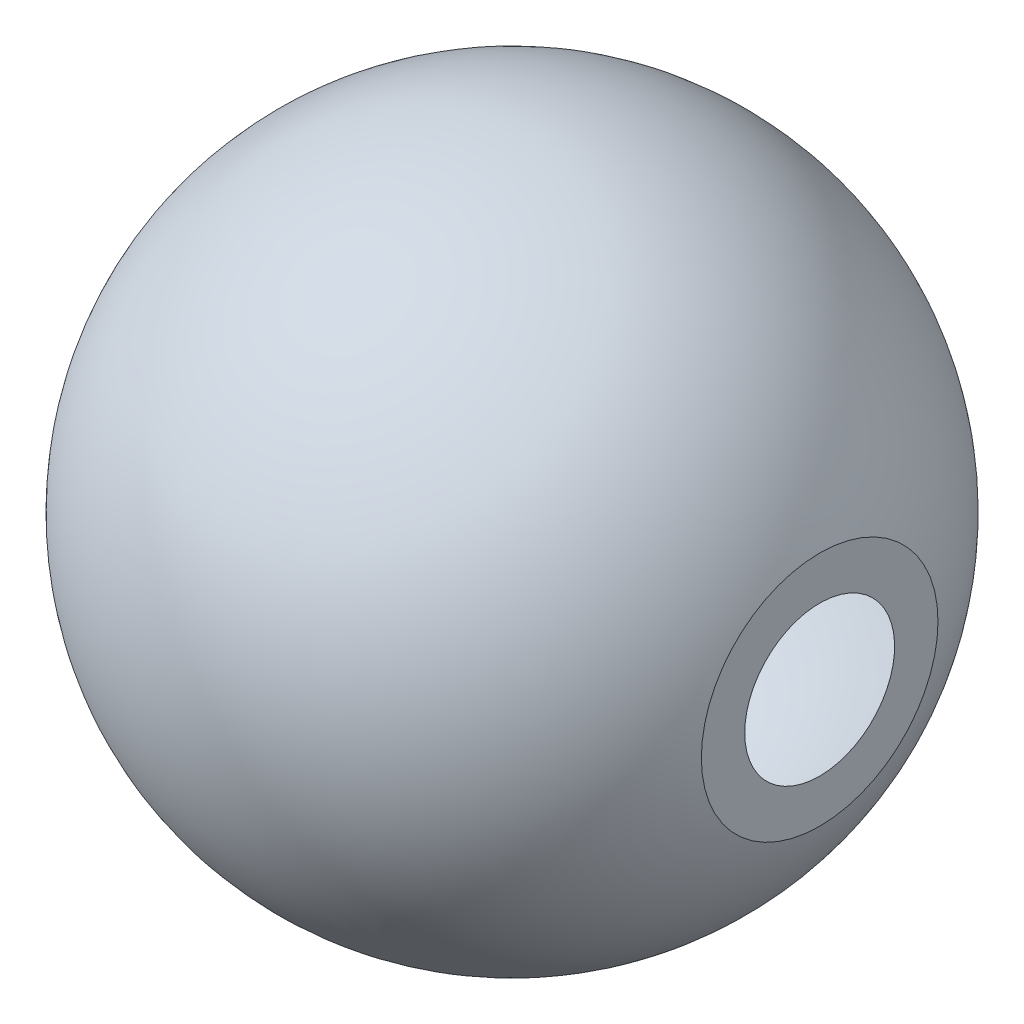
SolidWorks part; units mm, degrees
ref_plane "Front Plane" through (0, 0, 0) normal (0, 0, 1) x (1, 0, 0)
ref_plane "Top Plane" through (0, 0, 0) normal (0, 1, 0) x (1, 0, 0)
ref_plane "Right Plane" through (0, 0, 0) normal (1, 0, 0) x (0, 0, -1)
sketch "Sketch2" plane through (0, 0, 0) normal (0, 0, 1) x (1, 0, 0)
  line L1 (-76.2, 0) -> (-73.2, 0)
  line L3 (71.12, 17.3259) -> (71.12, 27.3567)
  arc A2 (71.12, 17.3259) -> (-73.2, 0) centre (0, 0) ccw
  spline S0 degree 4 poles (-76.2, 0) (-76.1997, 3.3499) (-75.8605, 9.1425) (-74.5492, 17.2684) (-71.3778, 27.3961) (-67.3503, 36.1749) (-62.292, 44.3214) (-56.2535, 51.7709) (-49.3299, 58.4059) (-41.6302, 64.1219) (-33.2754, 68.829) (-24.3971, 72.4532) (-15.1349, 74.9374) (-5.6389, 76.242) (3.9415, 76.3482) (13.4556, 75.2562) (22.7546, 72.9848) (31.6968, 69.5691) (40.1421, 65.0628) (47.958, 59.5363) (55.022, 53.0767) (61.2234, 45.7846) (66.4649, 37.7755) (70.6909, 29.1183) (74.2549, 18.6426) (75.7815, 10.0778) (76.1997, 3.8259) (76.2, 0) knots 0 0 0 0 0 0.055863 0.096966 0.136917 0.176869 0.216822 0.256775 0.296729 0.336682 0.376635 0.416588 0.456542 0.496495 0.536377 0.576259 0.616141 0.656023 0.695905 0.735787 0.775669 0.815551 0.855432 0.895313 0.936199 1 1 1 1 1 construction
  spline S1 degree 4 poles (-76.2, 0) (-76.1997, 3.3499) (-75.8605, 9.1425) (-74.5492, 17.2684) (-71.3778, 27.3961) (-67.3503, 36.1749) (-62.292, 44.3214) (-56.2535, 51.7709) (-49.3299, 58.4059) (-41.6302, 64.1219) (-33.2754, 68.829) (-24.3971, 72.4532) (-15.1349, 74.9374) (-5.6389, 76.242) (3.9415, 76.3482) (13.4556, 75.2562) (22.7546, 72.9848) (31.6968, 69.5691) (40.1421, 65.0628) (47.958, 59.5363) (55.022, 53.0767) (61.2234, 45.7846) (66.0641, 38.3879) (68.9642, 32.6343) (70.5252, 28.9028) (71.12, 27.3567) knots 0 0 0 0 0 0.055863 0.096966 0.136917 0.176869 0.216822 0.256775 0.296729 0.336682 0.376635 0.416588 0.456542 0.496495 0.536377 0.576259 0.616141 0.656023 0.695905 0.735787 0.775669 0.815551 0.855432 0.883114 0.883114 0.883114 0.883114 0.883114
  point P5 (71.12, 27.3567)
  dimension "D1" = 73.2
  dimension "D2" = 71.12
revolve "Revolve1" add sketch "Sketch2" angle 360 about L1
